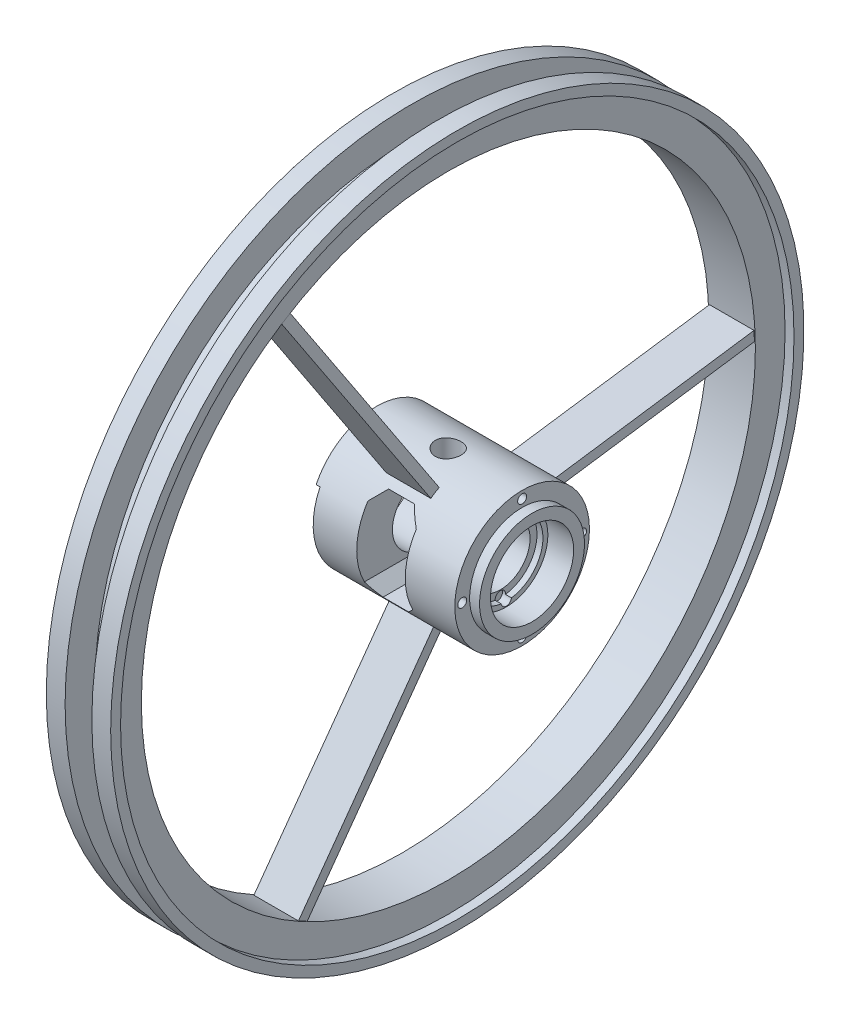
SolidWorks part; units mm, degrees
ref_plane "Front Plane" through (0, 0, 0) normal (0, 0, 1) x (1, 0, 0)
ref_plane "Top Plane" through (0, 0, 0) normal (0, 1, 0) x (1, 0, 0)
ref_plane "Right Plane" through (0, 0, 0) normal (1, 0, 0) x (0, 0, -1)
sketch "Sketch17" plane through (0, 0, 0) normal (0, 0, 1) x (1, 0, 0)
  line L0 (0, 0) -> (156.5215, 0) construction
sketch "Sketch1" plane through (0, 0, 0) normal (1, 0, 0) x (0, 0, -1)
  circle A0 centre (0, 0) radius 68
extrude "Boss-Extrude1" add sketch "Sketch1" along normal blind 157 contours A0
sketch "Sketch2" plane through (0, 0, 0) normal (-1, 0, 0) x (0, 0, 1)
  circle A0 centre (0, 0) radius 26
extrude "Cut-Extrude1" cut sketch "Sketch2" against normal up to next
sketch "Sketch3" plane through (0, 0, 0) normal (-1, 0, 0) x (0, 0, 1)
  line L1 (-68, 30) -> (68, 30)
  line L2 (-68, 30) -> (-68, -68)
  line L3 (-68, -68) -> (68, -68)
  line L4 (68, 30) -> (68, -68)
  circle A2 centre (0, 0) radius 68 construction
  circle A3 centre (0, 0) radius 26 construction
  dimension "D1" = 30
  dimension "D2" = 68
  dimension "D3" = 42
  dimension "D4" = 68
  dimension "D5" = 68
extrude "Cut-Extrude2" cut sketch "Sketch3" against normal blind 4 contours L2 L3 L4 L1
sketch "Sketch4" plane through (4, 0, 0) normal (-1, 0, 0) x (0, 0, 1)
  line L3 (-13.5, 29) -> (13.5, 29)
  arc A2 (13.5, 29) -> (-13.5, 29) centre (0, 0) cw
  dimension "D1" = 27
  dimension "D2" = 29
extrude "Cut-Extrude3" cut sketch "Sketch4" against normal blind 44
sketch "Sketch7" plane through (157, 0, 0) normal (1, 0, 0) x (0, 0, -1)
  circle A0 centre (0, 0) radius 42
extrude "Cut-Extrude4" cut sketch "Sketch7" against normal blind 26
sketch "Sketch8" plane through (131, 0, 0) normal (1, 0, 0) x (0, 0, -1)
  circle A0 centre (0, 0) radius 37
extrude "Cut-Extrude5" cut sketch "Sketch8" against normal blind 6 contours A0
sketch "Sketch9" plane through (125, 0, 0) normal (1, 0, 0) x (0, 0, -1)
  circle A0 centre (0, 0) radius 30
extrude "Cut-Extrude6" cut sketch "Sketch9" against normal blind 30 contours A0
ref_plane "Plane2" through (0, 0, 68) normal (0, 0, 1) x (1, 0, 0)
sketch "Sketch12" plane through (0, 0, 68) normal (0, 0, 1) x (1, 0, 0)
  line L0 (48, 37.576) -> (48, -31.4216)
  line L1 (48, -31.4216) -> (59.3739, -42.7955)
  line L2 (59.3739, -42.7955) -> (85.3739, -42.7955)
  line L3 (85.3739, -42.7955) -> (97, -31.1695)
  line L4 (97, -31.1695) -> (97, 37.3239)
  line L5 (97, 37.3239) -> (85.3739, 48.9499)
  line L6 (85.3739, 48.9499) -> (59.3739, 48.9499)
  line L7 (59.3739, 48.9499) -> (48, 37.576)
  line L8 (157, -68) -> (157, 68) construction
  line L9 (4, 30) -> (4, -68) construction
  dimension "D1" = 60
  dimension "D2" = 44
  dimension "D3" = 26
  dimension "D4" = 26
  dimension "D5" = 135
  dimension "D6" = 135
  dimension "D7" = 135
  dimension "D8" = 135
extrude "Cut-Extrude8" cut sketch "Sketch12" against normal blind 71 contours L0 L1 L2 L3 L4 L5 L6 L7
sketch "Sketch16" plane through (0, 0, 0) normal (-1, 0, 0) x (0, 0, 1)
  line L0 (35.9404, 57.726) -> (61.0246, 30) construction
  line L1 (35.9404, 57.726) -> (0, 68) construction
  arc A0 (61.0246, 30) -> (-61.0246, 30) centre (0, 0) ccw construction
  dimension "D1" = 37.38
  dimension "D2" = 37.3892
ref_plane "Plane5" through (0, 68, 0) normal (0, 1, 0) x (1, 0, 0)
sketch "Sketch23" plane through (0, 68, 0) normal (0, 1, 0) x (1, 0, 0)
  point P9 (72.3739, 0)
  point P10 (78.2608, 0)
  point P11 (0, 0)
  point P12 (0, 0)
  point P13 (0, 0)
  dimension "D1" = 13
hole_wizard "Tap Drill for M1.2x0.25 Tap1" positions "Sketch23" profile "Sketch26" hole size "M1.2x0.25" standard "ISO"
sketch "Sketch26" plane through (72.3739, 68, 0) normal (1, 0, 0) x (0, 0, 1)
  line L0 (0, 0) -> (0, 68)
  line L1 (0, 68) -> (13, 68)
  line L2 (13, 68) -> (13, 0)
  line L5 (13, 0) -> (0, 0)
  line L10 (0, 68) -> (-13, 68) construction
  line L11 (0, -6.35) -> (0, 107.95) construction
  dimension "Hole Dia." = 26
  dimension "Hole Depth" = 68
  dimension "Drill Angle" = 180
sketch "Sketch27" plane through (157, 0, 0) normal (1, 0, 0) x (0, 0, -1)
  circle A0 centre (0, 0) radius 68
  circle A1 centre (0, 0) radius 53
  dimension "D1" = 136
  dimension "D2" = 106
extrude "Cut-Extrude9" cut sketch "Sketch27" against normal blind 10
sketch "Sketch29" plane through (147, 0, 0) normal (1, 0, 0) x (0, 0, -1)
  line L0 (0, 68) -> (0, 53) construction
  line L1 (53, 0) -> (68, 0) construction
  line L2 (0, -53) -> (0, -68) construction
  line L3 (-53, 0) -> (-68, 0) construction
  line L4 (-68, 86.35) -> (-68, -86.35) construction
  circle A0 centre (0, 0) radius 53 construction
  circle A1 centre (0, 0) radius 53 construction
  circle A2 centre (0, 0) radius 68 construction
  point P21 (0, 60.5)
  point P23 (60.5, 0)
  point P25 (0, -60.5)
  point P27 (-60.5, 0)
hole_wizard "M8 Clearance Hole1" positions "Sketch29" profile "Sketch30" hole size "M8" standard "ISO"
sketch "Sketch30" plane through (147, 0, 60.5) normal (0, 1, 0) x (0, 0, -1)
  line L0 (0, 0) -> (0, 37.7039)
  line L1 (0, 37.7039) -> (4.5, 35)
  line L2 (4.5, 35) -> (4.5, 0)
  line L5 (4.5, 0) -> (0, 0)
  line L10 (0, 37.7039) -> (-4.5, 35) construction
  line L11 (0, -6.35) -> (0, 107.95) construction
  dimension "Hole Dia." = 9
  dimension "Hole Depth" = 35
  dimension "Drill Angle" = 118
ref_plane "Plane4" through (0, 0, 0) normal (0, 0.5285, -0.8489) x (-1, 0, 0)
sketch "Sketch19" plane through (0, 0, 0) normal (0, 0.5285, -0.8489) x (-1, 0, 0)
  line L3 (-26.5195, 310) -> (-71.5195, 310)
  line L7 (-97, 30.0991) -> (-97, 61.7272) construction
  line L8 (-48, 30.3131) -> (-48, 61.8533) construction
  line L9 (0, 0) -> (-156.5215, 0) construction
  line L10 (-71.5195, 310) -> (-95, 66.5)
  line L11 (-95, 66.5) -> (-50, 66.5)
  line L12 (-50, 66.5) -> (-26.5195, 310)
  line L13 (0, 68) -> (-147, 68) construction
  dimension "D2" = 49
  dimension "D1" = 310
  dimension "D3" = 45
  dimension "D4" = 1.5
  dimension "D5" = 2
sketch "Sketch21" plane through (0, 0, 0) normal (0, 0.5285, -0.8489) x (-1, 0, 0)
  line L0 (-71.5195, 310) -> (-72.5195, 310)
  line L1 (-72.5195, 310) -> (-72.5195, 340)
  line L2 (-72.5195, 340) -> (-81.5195, 340)
  line L3 (-81.5195, 340) -> (-81.5195, 350)
  line L4 (-81.5195, 350) -> (-62.5195, 350)
  line L5 (-16.5195, 350) -> (-16.5195, 340)
  line L6 (-16.5195, 340) -> (-25.5195, 340)
  line L7 (-25.5195, 340) -> (-25.5195, 310)
  line L8 (-25.5195, 310) -> (-26.5195, 310)
  line L11 (-62.5195, 350) -> (-62.5195, 320)
  line L12 (-62.5195, 320) -> (-35.5195, 320)
  line L13 (-35.5195, 320) -> (-35.5195, 350)
  line L14 (-35.5195, 350) -> (-16.5195, 350)
  line L15 (-26.5195, 310) -> (-71.5195, 310) construction
  line L17 (-71.5195, 310) -> (-26.5195, 310)
  dimension "D2" = 10
  dimension "D3" = 10
  dimension "D5" = 1
  dimension "D1" = 10
  dimension "D6" = 10
  dimension "D7" = 10
  dimension "D8" = 65
  dimension "D9" = 27
  dimension "D10" = 9
  dimension "D11" = 40
  dimension "D12" = 40
revolve "Revolve1" add sketch "Sketch21" angle 360 about L0
extrude "Boss-Extrude4" add sketch "Sketch19" along normal mid plane 10
pattern_circular "CirPattern4" count 3 over 360 about axis through (0, 0, 0) along (1, 0, 0) of "Boss-Extrude4"
sketch "Esquisse4" plane through (131, 0, 0) normal (1, 0, 0) x (0, 0, -1)
  line L0 (0, 0) -> (0, -36) construction
  point P11 (0, -36)
  dimension "D1" = 36
  dimension "D2" = 0
hole_wizard "M10 Clearance Hole1" positions "Esquisse4" profile "Esquisse6" hole size "M10" standard "ANSI Metric"
sketch "Esquisse6" plane through (131, -36, 0) normal (0, 1, 0) x (0, 0, -1)
  line L0 (0, 0) -> (0, 9)
  line L1 (0, 9) -> (5.25, 9)
  line L2 (5.25, 9) -> (5.25, 0)
  line L5 (5.25, 0) -> (0, 0)
  line L10 (0, 9) -> (-5.25, 9) construction
  line L11 (0, -6.35) -> (0, 107.95) construction
  dimension "Hole Dia." = 10.5
  dimension "Hole Depth" = 9
  dimension "Drill Angle" = 180
equation "\"D1@Sketch3\"=26+8/2"
equation "\"D2@Sketch3\"=26+\"D3@Sketch3\""
equation "\"D4@Sketch3\"=\"D2@Sketch3\""
equation "\"D5@Sketch3\"=\"D2@Sketch3\""
equation "\"D5@Sketch19\"=(\"D2@Sketch19\"-\"D3@Sketch19\")/2"
equation "\"D10@Sketch21\"=(\"D8@Sketch21\"-\"D9@Sketch21\")/2-10"
equation "\"D12@Sketch21\"=\"D11@Sketch21\""
equation "\"D2@Sketch27\"=\"D1@Sketch27\"-15*2"
